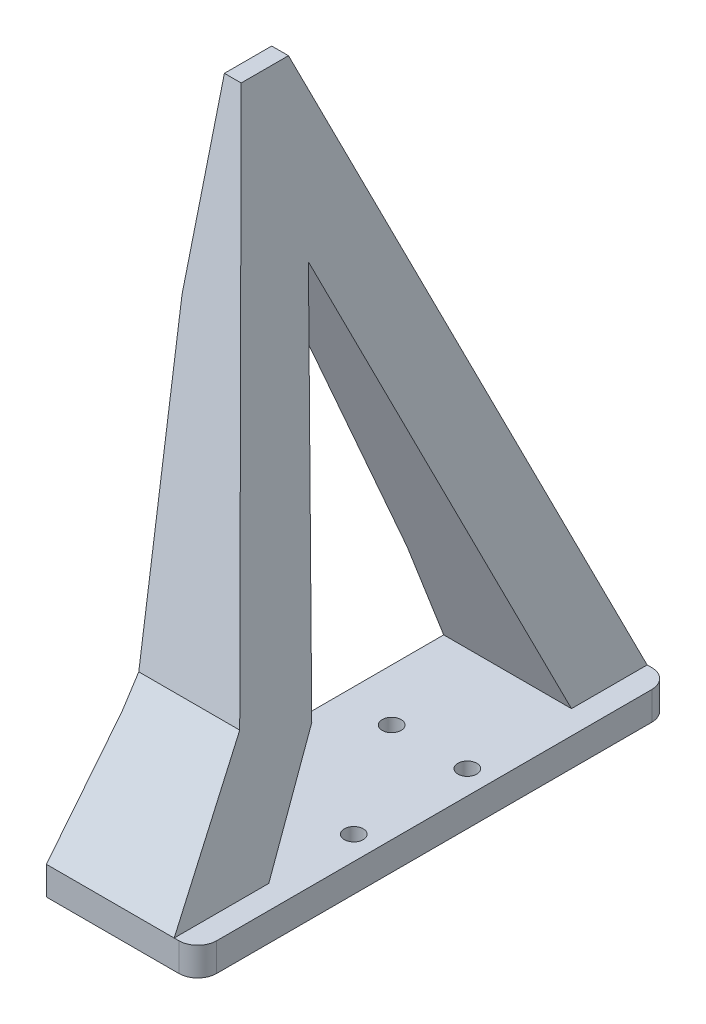
SolidWorks part; units mm, degrees
ref_plane "前视基准面" through (0, 0, 0) normal (0, 0, 1) x (1, 0, 0)
ref_plane "上视基准面" through (0, 0, 0) normal (0, 1, 0) x (1, 0, 0)
ref_plane "右视基准面" through (0, 0, 0) normal (1, 0, 0) x (0, 0, -1)
sketch "草图1" plane through (0, 0, 0) normal (0, 1, 0) x (1, 0, 0)
  line L0 (2.75, 0) -> (0, 0) construction
  line L1 (-9.25, 25) -> (7.25, 25)
  line L2 (-9.25, 25) -> (-9.25, -25)
  line L3 (-9.25, -25) -> (7.25, -25)
  line L4 (9.25, 23) -> (9.25, -23)
  line L5 (-9.25, 25) -> (9.25, -25) construction
  line L6 (-9.25, -25) -> (9.25, 25) construction
  line L7 (-1.25, 6) -> (6.75, 6) construction
  line L8 (-1.25, 6) -> (-1.25, -6) construction
  line L9 (-1.25, -6) -> (6.75, -6) construction
  line L10 (6.75, 6) -> (6.75, -6) construction
  line L11 (-1.25, 6) -> (6.75, -6) construction
  line L12 (-1.25, -6) -> (6.75, 6) construction
  circle A0 centre (-1.25, 6) radius 1
  circle A1 centre (-1.25, -6) radius 1
  circle A2 centre (6.75, -6) radius 1
  circle A3 centre (6.75, 6) radius 1
  arc A5 (7.25, -25) -> (9.25, -23) centre (7.25, -23) ccw
  arc A6 (7.25, 25) -> (9.25, 23) centre (7.25, 23) cw
  point P0 (0, 0)
  point P6 (2.75, 0)
  dimension "D3" = 2
  dimension "D1" = 12
  dimension "D2" = 8
  dimension "D4" = 8
  dimension "D5" = 5
  dimension "D6" = 50
extrude "凸台-拉伸1" add sketch "草图1" along normal blind 3
sketch "草图2" plane through (0, 3, 0) normal (0, 1, 0) x (1, 0, 0)
  line L0 (-9.25, -25) -> (7.25, -25) construction
  line L1 (6.7578, -25) -> (-9.25, -25)
  line L2 (6.7578, -25) -> (6.7578, 25)
  line L3 (6.7578, 25) -> (-9.25, 25)
  line L4 (-9.25, -25) -> (-9.25, 25)
  line L5 (6.7578, -25) -> (-9.25, 25) construction
  line L6 (6.7578, 25) -> (-9.25, -25) construction
  point P0 (-1.2461, 0)
extrude "凸台-拉伸2" add sketch "草图2" along normal blind 80
sketch "草图3" plane through (6.7578, 0, 0) normal (1, 0, 0) x (0, 0, -1)
  line L0 (-25, 3) -> (-15, 15.5)
  line L1 (25, 3) -> (1.8182, 63)
  line L2 (0, 0) -> (0, 36.8077) construction
  line L3 (-15, 3) -> (-8, 13)
  line L4 (-8, 13) -> (0, 47)
  line L5 (-25, 3) -> (25, 3) construction
  line L6 (25, 0) -> (-25, 0) construction
  line L7 (1.8182, 63) -> (-3.1818, 63)
  line L8 (-3.1818, 63) -> (-15, 15.5)
  line L9 (0, 47) -> (17, 3)
  line L10 (-15, 3) -> (17, 3)
  line L11 (-25, 3) -> (-39.0868, 3)
  line L12 (-39.0868, 3) -> (-39.0868, 88.1336)
  line L13 (-39.0868, 88.1336) -> (32.7843, 88.1336)
  line L14 (32.7843, 88.1336) -> (32.7843, 3)
  line L15 (32.7843, 3) -> (25, 3)
  dimension "D1" = 10
  dimension "D2" = 15.5
  dimension "D3" = 15
  dimension "D4" = 8
  dimension "D5" = 13
  dimension "D6" = 47
  dimension "D7" = 8
  dimension "D8" = 5
  dimension "D9" = 60
extrude "切除-拉伸1" cut sketch "草图3" against normal through all
sketch "草图4" plane through (0, 0, 25) normal (0, 0, 1) x (1, 0, 0)
  line L0 (6.7578, 3) -> (6.7578, 67.7633)
  line L1 (6.7578, 67.7633) -> (-9.1496, 67.7633)
  line L2 (-9.1496, 67.7633) -> (6.7578, 3)
  dimension "D1" = 103.8
extrude "切除-拉伸2" cut sketch "草图4" against normal through all
sketch "草图5" plane through (-9.25, 0, 0) normal (-1, 0, 0) x (0, 0, 1)
  line L0 (0, 47) -> (-17, 3)
  line L1 (-17, 3) -> (15, 3)
  line L2 (15, 3) -> (8, 13)
  line L3 (8, 13) -> (0, 47)
  line L4 (-1.8182, 63) -> (-25, 3)
  line L5 (-25, 3) -> (-25, 0)
  line L6 (-25, 0) -> (25, 0)
  line L7 (25, 0) -> (25, 3)
  line L8 (25, 3) -> (15, 15.5)
  line L9 (15, 15.5) -> (3.1818, 63)
  line L10 (3.1818, 63) -> (-1.8182, 63)
extrude "凸台-拉伸3" add sketch "草图5" along normal blind 3
sketch "草图6" plane through (0, 0, -25) normal (0, 0, -1) x (-1, 0, 0)
  line L0 (6.75, 0) -> (6.75, 13)
  line L1 (-7.25, 0) -> (12.25, 0) construction
  line L2 (6.75, 13) -> (9.75, 45)
  line L3 (9.75, 45) -> (9.75, 64.871)
  line L4 (9.75, 64.871) -> (14.0936, 64.871)
  line L5 (14.0936, 64.871) -> (14.0936, 0)
  line L6 (14.0936, 0) -> (6.75, 0)
  line L7 (12.25, 13) -> (-4.3015, 13) construction
  line L8 (12.25, 63) -> (12.25, 3) construction
  line L9 (12.25, 63) -> (7.9797, 63) construction
  point P8 (0, 0)
  point P15 (14.0936, 64.871)
  dimension "D1" = 5.5
  dimension "D2" = 2.5
  dimension "D3" = 18
extrude "切除-拉伸3" cut sketch "草图6" against normal through all
